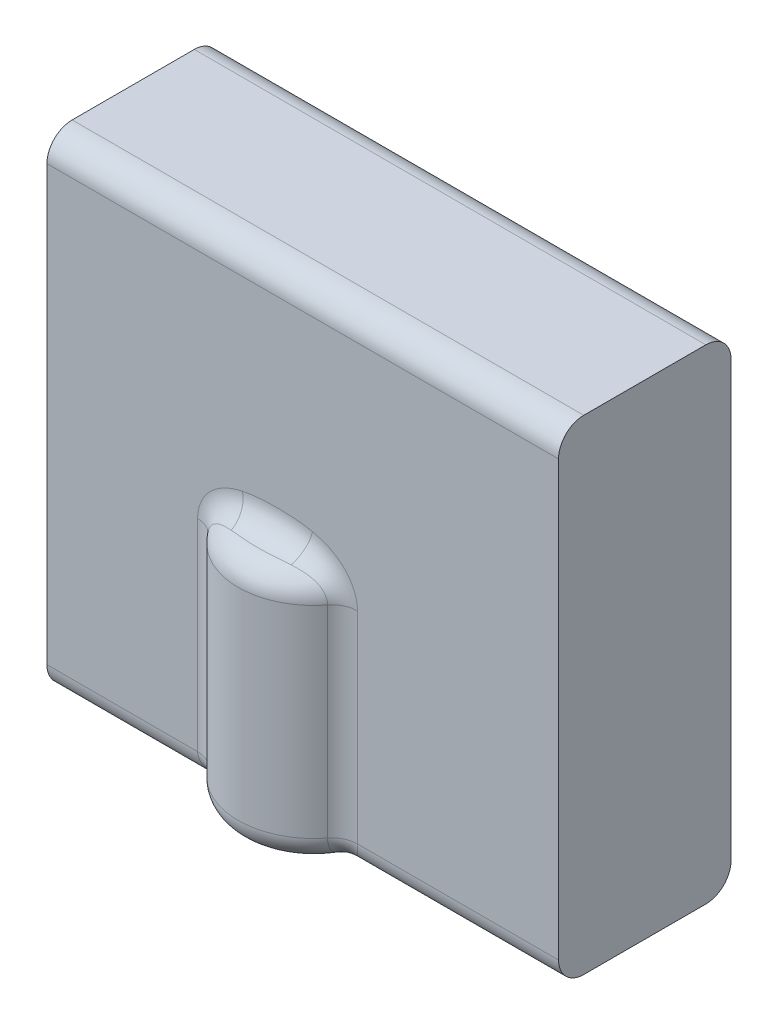
SolidWorks part; units mm, degrees
material "PA Type 6"
ref_plane "Front Plane" through (0, 0, 0) normal (0, 0, 1) x (1, 0, 0)
ref_plane "Top Plane" through (0, 0, 0) normal (0, 1, 0) x (1, 0, 0)
ref_plane "Right Plane" through (0, 0, 0) normal (1, 0, 0) x (0, 0, -1)
sketch "Sketch1" plane through (0, 0, 0) normal (0, 0, 1) x (1, 0, 0)
  line L1 (-12.8778, 12.192) -> (12.8778, 12.192)
  line L2 (-12.8778, 12.192) -> (-12.8778, -12.192)
  line L3 (-12.8778, -12.192) -> (12.8778, -12.192)
  line L4 (12.8778, 12.192) -> (12.8778, -12.192)
  point P4 (-12.8778, 0)
  point P6 (0, 12.192)
  dimension "D1" = 25.7556
  dimension "D2" = 24.384
extrude "Boss-Extrude1" add sketch "Sketch1" along normal blind 8.6868
sketch "Sketch3" plane through (0, -12.192, 0) normal (0, -1, 0) x (1, 0, 0)
  line L0 (-12.8778, 0) -> (12.8778, 0) construction
  circle A0 centre (-1.27, 6.858) radius 3.81
  dimension "D1" = 7.62
  dimension "D2" = 6.858
  dimension "D3" = 1.27
  dimension "D4" = 10.668
extrude "Boss-Extrude2" add sketch "Sketch3" against normal blind 12.7
fillet "Fillet3" radius 1.27 5 edges at (0, 12.192, 0) (0, 12.192, 8.6868) (0, -12.192, 0) (-8.7451, -12.192, 8.6868) (7.4751, -12.192, 8.6868)
fillet "Fillet4" radius 1.27 2 edges at (-1.27, 0.508, 10.668) (-1.27, -12.192, 10.668)
fillet "Fillet5" radius 1.27 7 edges at (1.7872, -11.9006, 8.2262) (2.0724, -5.842, 8.6868) (1.5673, 0.1944, 8.6868) (-1.27, 0.508, 8.6868) (-4.3598, -0.0483, 8.6868) (-4.3272, -11.9006, 8.2262) (-4.6124, -5.842, 8.6868)
